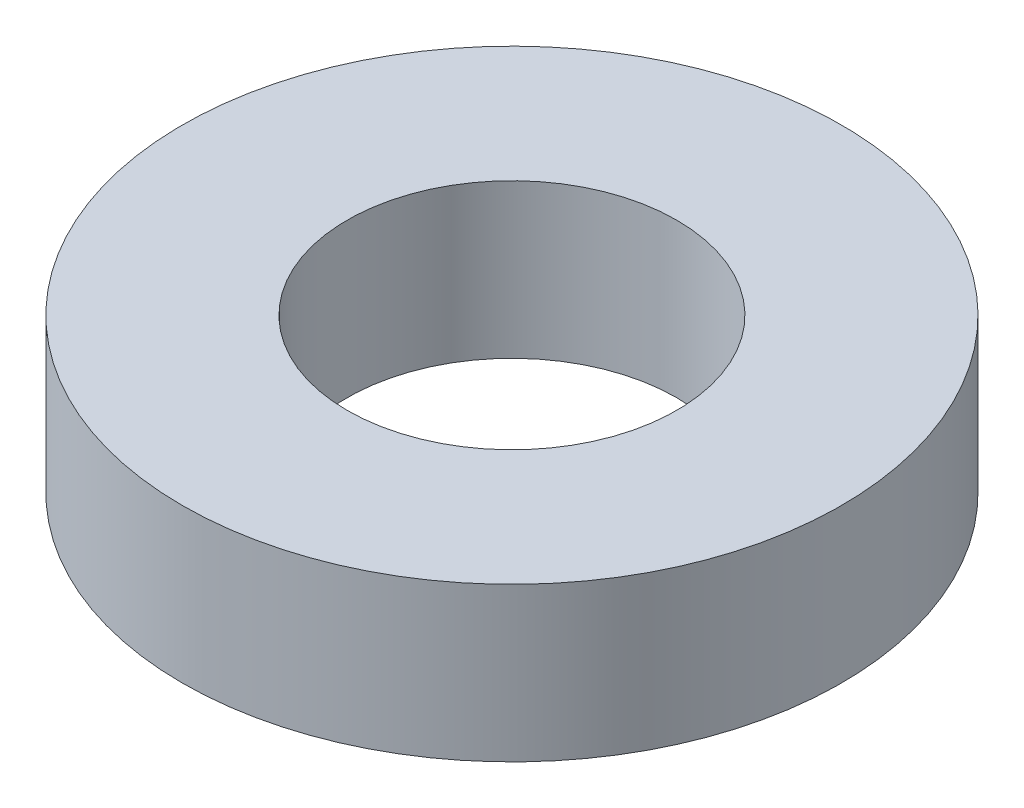
SolidWorks part; units mm, degrees
ref_plane "Front Plane" through (0, 0, 0) normal (0, 0, 1) x (1, 0, 0)
ref_plane "Top Plane" through (0, 0, 0) normal (0, 1, 0) x (1, 0, 0)
ref_plane "Right Plane" through (0, 0, 0) normal (1, 0, 0) x (0, 0, -1)
sketch "Sketch1" plane through (0, 0, 0) normal (0, 1, 0) x (1, 0, 0)
  circle A0 centre (0, 0) radius 30
  dimension "FLANGE_OD" = 60
extrude "Boss-Extrude1" add sketch "Sketch1" along normal blind 14
sketch "Sketch2" plane through (0, 0, 0) normal (0, 1, 0) x (1, 0, 0)
  circle A0 centre (0, 0) radius 15
  dimension "BORE_D" = 30
extrude "Cut-Extrude1" cut sketch "Sketch2" along normal through all
sketch "Sketch3" plane through (0, 14, 0) normal (0, 1, 0) x (1, 0, 0)
  circle A0 centre (0, 0) radius 9.9757 construction
  circle A1 centre (-9.9757, 0) radius 2.5049
  dimension "BOLT_D" = 5.0099
  dimension "BOLT_PCD" = 19.9513
extrude "Cut-Extrude2" cut sketch "Sketch3" against normal blind 10.9538 rebuild error yes
pattern_circular "CirPattern1" count 8 over 360 rebuild error yes
